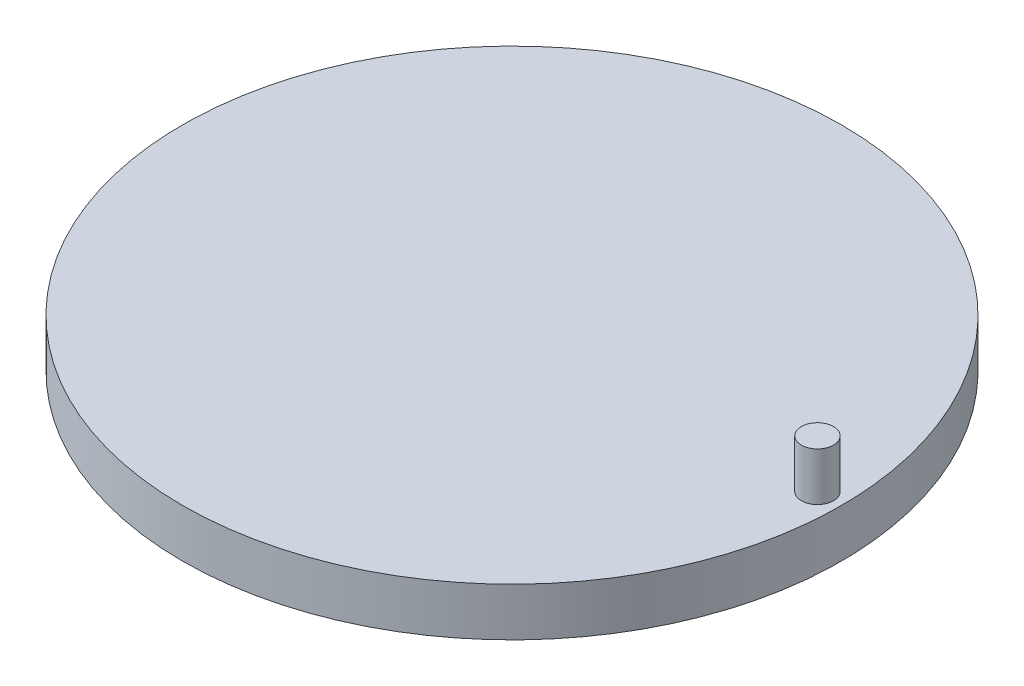
SolidWorks part; units mm, degrees
ref_plane "Ön Düzlem" through (0, 0, 0) normal (0, 0, 1) x (1, 0, 0)
ref_plane "Üst Düzlem" through (0, 0, 0) normal (0, 1, 0) x (1, 0, 0)
ref_plane "Sağ Düzlem" through (0, 0, 0) normal (1, 0, 0) x (0, 0, -1)
sketch "Çizim2" plane through (0, 0, 0) normal (0, 1, 0) x (1, 0, 0)
  circle A0 centre (0, 0) radius 20.5
  circle A1 centre (19, 0) radius 1
  dimension "D2" = 41
  dimension "D3" = 2
  dimension "D1" = 19
extrude "Yükseklik-Ekstrüzyon1" add sketch "Çizim2" along normal blind 3 contours A1 | A0
extrude "Yükseklik-Ekstrüzyon2" add sketch "Çizim2<3>" along normal blind 6 contours A1 region at (19, 0, 0)
sketch "Çizim2<3>" plane through (0, 0, 0) normal (0, 1, 0) x (1, 0, 0) same geometry as "Çizim2"
